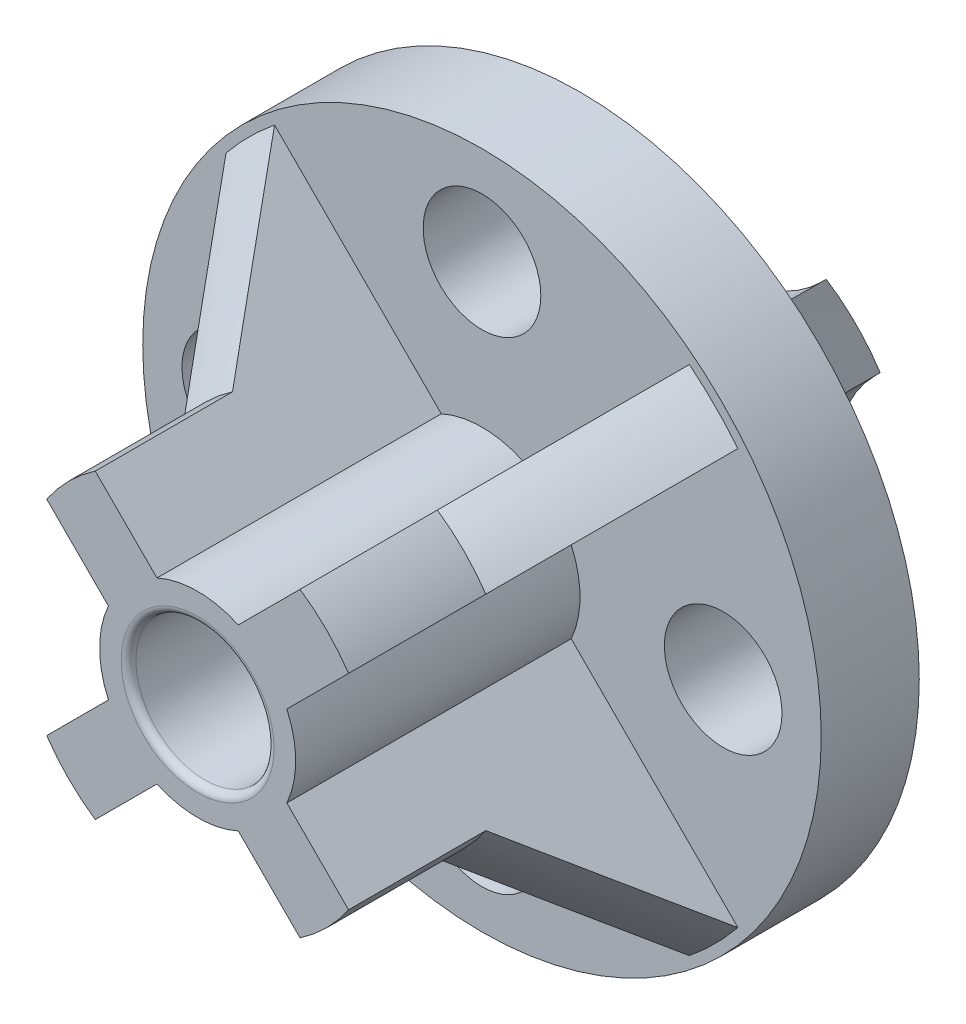
SolidWorks part; units mm, degrees
ref_plane "Front Plane" through (0, 0, 0) normal (0, 0, 1) x (1, 0, 0)
ref_plane "Top Plane" through (0, 0, 0) normal (0, 1, 0) x (1, 0, 0)
ref_plane "Right Plane" through (0, 0, 0) normal (1, 0, 0) x (0, 0, -1)
sketch "Sketch2" plane through (0, 0, 0) normal (0, 0, 1) x (1, 0, 0)
  line L0 (0, 0) -> (0, 24.6) construction
  line L1 (0, 0) -> (24.6, 0) construction
  line L2 (0, 0) -> (0, -24.6) construction
  line L3 (0, 0) -> (-24.6, 0) construction
  circle A0 centre (0, 0) radius 2
  circle A1 centre (0, 24.6) radius 6
  circle A2 centre (0, -24.6) radius 6
  circle A3 centre (-24.6, 0) radius 6
  circle A4 centre (24.6, 0) radius 6
  circle A5 centre (0, 0) radius 33.6
  dimension "D1" = 12
  dimension "D3" = 67.2
  dimension "D4" = 4
  dimension "D2" = 24.6
extrude "Boss-Extrude1" add sketch "Sketch2" along normal blind 10
sketch "Sketch3" plane through (0, 0, 0) normal (0, 0, -1) x (-1, 0, 0)
  line L0 (-8, 0) -> (-11.1, 0)
  line L1 (5.6569, 5.6569) -> (-5.6569, 5.6569) construction
  line L2 (5.6569, 5.6569) -> (5.6569, -5.6569) construction
  line L3 (5.6569, -5.6569) -> (-5.6569, -5.6569) construction
  line L4 (-5.6569, 5.6569) -> (-5.6569, -5.6569) construction
  line L5 (5.6569, 5.6569) -> (-5.6569, -5.6569) construction
  line L6 (5.6569, -5.6569) -> (-5.6569, 5.6569) construction
  line L7 (-5.6569, -5.6569) -> (-23.7588, -23.7588) construction
  line L8 (0, -8) -> (0, -11.1)
  line L11 (-41.0226, -6.4949) -> (-6.4949, -41.0226) construction
  line L20 (-21.0047, -26.5128) -> (-2.1871, -7.6952) construction
  line L21 (-26.5128, -21.0047) -> (-7.6952, -2.1871) construction
  line L30 (-26.3527, -20.8446) -> (-15.0541, -9.5459)
  line L31 (-20.8446, -26.3527) -> (-9.5459, -15.0541)
  circle A0 centre (24.6, 0) radius 13.5 construction
  circle A1 centre (0, -24.6) radius 13.5 construction
  circle A2 centre (-24.6, 0) radius 13.5 construction
  circle A3 centre (0, 24.6) radius 13.5 construction
  circle A4 centre (0, 0) radius 8 construction
  circle A5 centre (0, 0) radius 33.6 construction
  arc A6 (0, -8) -> (-8, 0) centre (0, 0) cw
  arc A7 (-26.3527, -20.8446) -> (-20.8446, -26.3527) centre (0, 0) ccw
  arc A8 (-9.5459, -15.0541) -> (0, -11.1) centre (0, -24.6) cw
  arc A9 (-15.0541, -9.5459) -> (-11.1, 0) centre (-24.6, 0) ccw
  point P28 (23.7588, 23.7588)
  point P31 (-23.7588, -23.7588)
  point P34 (23.7588, -23.7588)
  point P37 (-23.7588, 23.7588)
  dimension "D1" = 16
  dimension "D2" = 27
extrude "Boss-Extrude2" add sketch "Sketch3" along normal blind 15
pattern_circular "CirPattern1" count 4 over 360 about axis through (0, 0, 0) along (0, 0, 1) of "Boss-Extrude2"
sketch "Sketch4" plane through (0, 0, 10) normal (0, 0, 1) x (1, 0, 0)
  line L0 (-3.6194, 6.05) -> (3.6194, 6.05) construction
  line L1 (0, 6.05) -> (0, 7.05) construction
  line L2 (-3.6194, 6.05) -> (3.6194, 6.05)
  line L3 (0, 6.05) -> (0, -7.05) construction
  circle A0 centre (0, 0) radius 10
  circle A1 centre (0, 0) radius 7.05 construction
  arc A2 (-3.6194, 6.05) -> (3.6194, 6.05) centre (0, 0) ccw
  dimension "D1" = 20
  dimension "D2" = 14.1
  dimension "D3" = 1
extrude "Boss-Extrude3" add sketch "Sketch4" along normal blind 29
sketch "Sketch5" plane through (0, 0, 0) normal (0, 0, -1) x (-1, 0, 0)
  circle A0 centre (0, 0) radius 33.6
  circle A1 centre (0, 0) radius 34.6
  dimension "D1" = 69.2
extrude "Boss-Extrude5" add sketch "Sketch5" against normal up to surface (10 mm away) up to face at (-18.6, 0, 10)
sketch "Sketch6" plane through (0, 0, 0) normal (0, 0, -1) x (-1, 0, 0)
  circle A0 centre (0, 0) radius 2
  circle A1 centre (0, 0) radius 8
  circle A2 centre (0, 0) radius 8 construction
  circle A3 centre (0, 0) radius 2 construction
extrude "Boss-Extrude6" add sketch "Sketch6" along normal blind 4
sketch "Sketch8" plane through (0, 0, 10) normal (0, 0, 1) x (1, 0, 0)
  line L0 (0, 0) -> (34.6, 0) construction
  line L1 (0, 0) -> (24.4659, -24.4659) construction
  line L2 (21.1547, -26.1044) -> (4.1489, -9.0987)
  line L3 (26.1044, -21.1547) -> (9.0987, -4.1489)
  line L4 (12.2329, -12.2329) -> (9.7581, -14.7078) construction
  line L5 (12.2329, -12.2329) -> (14.7078, -9.7581) construction
  circle A0 centre (0, 0) radius 34.6 construction
  arc A1 (26.1044, -21.1547) -> (21.1547, -26.1044) centre (0, 0) cw
  circle A2 centre (0, 0) radius 33.6 construction
  circle A3 centre (0, 0) radius 10 construction
  arc A4 (9.0987, -4.1489) -> (4.1489, -9.0987) centre (0, 0) cw
  circle A5 centre (0, 0) radius 10 construction
  dimension "D2" = 67.2
  dimension "D1" = 45
  dimension "D3" = 3.5
extrude "Boss-Extrude7" add sketch "Sketch8" along normal blind 15
pattern_circular "CirPattern2" count 4 over 360 about axis through (0, 0, 10) along (0, 0, -1) of "Boss-Extrude7"
chamfer "Chamfer1" distance 15 angle 45 4 edges at (23.7588, 23.7588, -15) (23.7588, -23.7588, -15) (-23.7588, -23.7588, -15) (-23.7588, 23.7588, -15)
chamfer "Chamfer2" distance 15 angle 45 4 edges at (23.7588, -23.7588, 25) (-23.7588, -23.7588, 25) (-23.7588, 23.7588, 25) (23.7588, 23.7588, 25)
sketch "Sketch9" plane through (0, 0, 25) normal (0, 0, 1) x (1, 0, 0)
  line L0 (4.1489, 9.0987) -> (10.4424, 15.3921)
  line L1 (15.3921, 10.4424) -> (9.0987, 4.1489)
  line L2 (10.4424, -15.3921) -> (4.1489, -9.0987)
  line L3 (15.3921, -10.4424) -> (9.0987, -4.1489)
  line L4 (-15.3921, -10.4424) -> (-9.0987, -4.1489)
  line L5 (-10.4424, -15.3921) -> (-4.1489, -9.0987)
  line L6 (-15.3921, 10.4424) -> (-9.0987, 4.1489)
  line L7 (-4.1489, 9.0987) -> (-10.4424, 15.3921)
  arc A0 (-10.4424, 15.3921) -> (-15.3921, 10.4424) centre (0, 0) ccw
  arc A1 (-4.1489, 9.0987) -> (-9.0987, 4.1489) centre (0, 0) ccw
  arc A2 (-9.0987, -4.1489) -> (-4.1489, -9.0987) centre (0, 0) ccw
  arc A3 (-15.3921, -10.4424) -> (-10.4424, -15.3921) centre (0, 0) ccw
  arc A4 (15.3921, -10.4424) -> (10.4424, -15.3921) centre (0, 0) cw
  arc A5 (4.1489, -9.0987) -> (9.0987, -4.1489) centre (0, 0) ccw
  arc A6 (4.1489, 9.0987) -> (9.0987, 4.1489) centre (0, 0) cw
  arc A7 (10.4424, 15.3921) -> (15.3921, 10.4424) centre (0, 0) cw
  circle A8 centre (0, 0) radius 10 construction
extrude "Boss-Extrude8" add sketch "Sketch9" along normal up to surface (14 mm away) up to face at (10, 0, 39)
sketch "Sketch10" plane through (0, 0, 39) normal (0, 0, 1) x (1, 0, 0)
  circle A0 centre (0, 0) radius 7.05
  dimension "D1" = 14.1
extrude "Cut-Extrude1" cut sketch "Sketch10" against normal blind 7
fillet "Fillet1" radius 0.75 2 edges at (7.05, 0, 39) (8, 0, -15)
